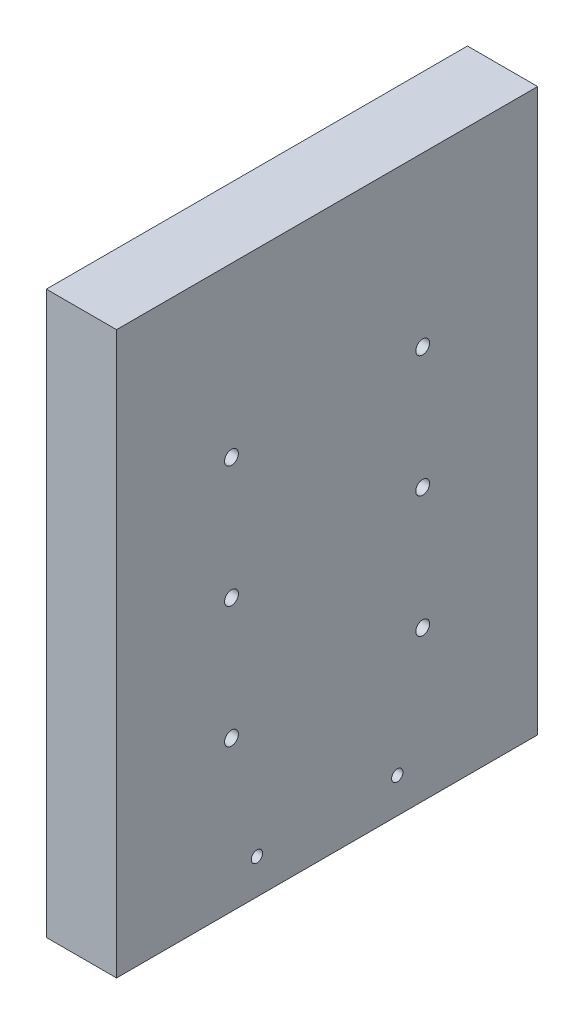
SolidWorks part; units mm, degrees
material "1060 Alloy"
ref_plane "Front Plane" through (0, 0, 0) normal (0, 0, 1) x (1, 0, 0)
ref_plane "Top Plane" through (0, 0, 0) normal (0, 1, 0) x (1, 0, 0)
ref_plane "Right Plane" through (0, 0, 0) normal (1, 0, 0) x (0, 0, -1)
sketch "Sketch2" plane through (0, 0, 0) normal (1, 0, 0) x (0, 0, -1)
  line L1 (-38.1, 0) -> (38.1, 0)
  line L2 (-38.1, 0) -> (-38.1, 101.6)
  line L3 (-38.1, 101.6) -> (38.1, 101.6)
  line L4 (38.1, 0) -> (38.1, 101.6)
  dimension "D1" = 76.2
  dimension "D2" = 101.6
extrude "Boss-Extrude2" add sketch "Sketch2" along normal blind 12.7
hole_wizard "Ø2.5mm Dowel Hole1" positions "Sketch4" profile "Sketch3" hole size "Ø2.5" standard "ANSI Metric" end condition through all
sketch "Sketch4" plane through (0, 0, 0) normal (-1, 0, 0) x (0, 0, 1)
  line L1 (38.1, 0) -> (-38.1, 0) construction
  point P0 (-17.3, 71.2)
  point P2 (-17.3, 49.2)
  point P4 (-17.3, 27.2)
  dimension "D1" = 22
  dimension "D2" = 22
  dimension "D3" = 27.2
  dimension "D4" = 17.3
sketch "Sketch3" plane through (0, 71.2, -17.3) normal (0, 1, 0) x (0, 0, 1)
  line L0 (0, 0) -> (0, 12.7)
  line L1 (0, 12.7) -> (1.25, 12.7)
  line L2 (1.25, 12.7) -> (1.25, 0)
  line L5 (1.25, 0) -> (0, 0)
  line L11 (0, -6.35) -> (0, 107.95) construction
  dimension "Thru Hole Dia." = 2.5
  dimension "Thru Hole Depth" = 12.7
mirror "Mirror1" about plane through (0, 0, 0) normal (0, 0, 1) of "Ø2.5mm Dowel Hole1"
sketch "Sketch5" plane through (0, 0, 0) normal (-1, 0, 0) x (0, 0, 1)
  circle A0 centre (0, 67.2) radius 5
  circle A1 centre (17.3, 71.2) radius 1.25 construction
  dimension "D1" = 10
  dimension "D2" = 17.3
  dimension "D3" = 4
extrude "Cut-Extrude1" cut sketch "Sketch5" against normal blind 2.5
sketch "Sketch15" plane through (12.7, 0, 0) normal (1, 0, 0) x (0, 0, -1)
  line L0 (-38.1, 0) -> (38.1, 0) construction
  line L1 (38.1, 0) -> (38.1, 101.6) construction
  line L2 (-38.1, 101.6) -> (-38.1, 0) construction
  circle A0 centre (12.7, 6.35) radius 0.95
  circle A1 centre (-12.7, 6.35) radius 0.95
  dimension "D1" = 1.9
  dimension "D2" = 1.9
  dimension "D3" = 6.35
  dimension "D4" = 6.35
  dimension "D5" = 25.4
  dimension "D6" = 25.4
hole_wizard "Tap Drill for M2.5x0.45 Tap1" positions "Sketch17" profile "Sketch16" hole size "M2.5x0.45" standard "ANSI Metric"
sketch "Sketch17" plane through (12.7, 0, 0) normal (1, 0, 0) x (0, 0, -1)
  point P0 (-12.7, 6.35)
  point P3 (12.7, 6.35)
sketch "Sketch16" plane through (12.7, 6.35, 12.7) normal (0, 1, 0) x (0, 0, -1)
  line L0 (0, 0) -> (0, 13.3159)
  line L1 (0, 13.3159) -> (1.025, 12.7)
  line L2 (1.025, 12.7) -> (1.025, 0)
  line L5 (1.025, 0) -> (0, 0)
  line L10 (0, 13.3159) -> (-1.025, 12.7) construction
  line L11 (0, -6.35) -> (0, 107.95) construction
  dimension "Hole Dia." = 2.05
  dimension "Hole Depth" = 12.7
  dimension "Drill Angle" = 118
